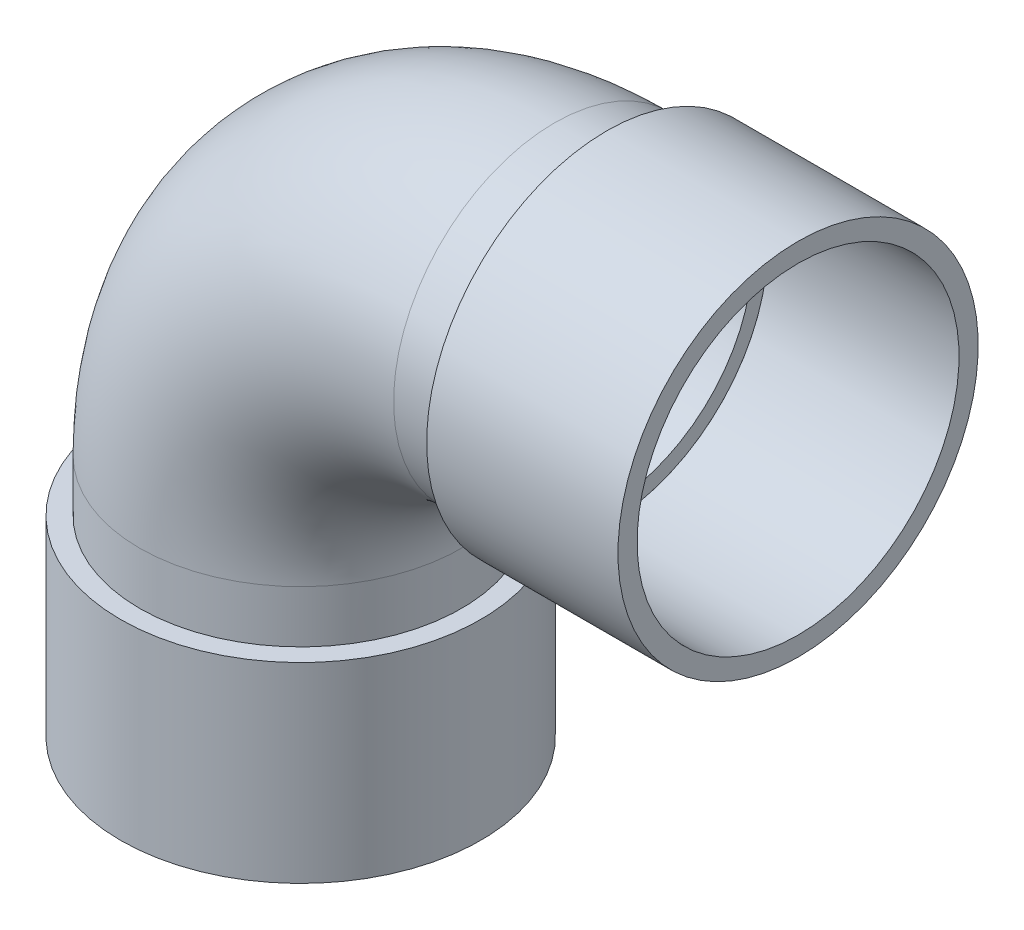
SolidWorks part; units mm, degrees
ref_plane "Alzado" through (0, 0, 0) normal (0, 0, 1) x (1, 0, 0)
ref_plane "Planta" through (0, 0, 0) normal (0, 1, 0) x (1, 0, 0)
ref_plane "Vista lateral" through (0, 0, 0) normal (1, 0, 0) x (0, 0, -1)
sketch "Croquis2" plane through (0, 0, 0) normal (0, 0, 1) x (1, 0, 0)
  line L0 (0, 0) -> (0, 27.27)
  line L1 (132.73, 160) -> (160, 160)
  arc A0 (0, 27.27) -> (132.73, 160) centre (132.73, 27.27) cw
  point P1 (0, 254)
  point P6 (0, 160)
  point P7 (-3.1791, 254)
  point P9 (0, 160)
  dimension "D3" = 132.73
  dimension "D1" = 160
  dimension "D2" = 160
sketch "Croquis3" plane through (0, 0, 0) normal (0, 1, 0) x (1, 0, 0)
  circle A0 centre (0, 0) radius 84.15
  circle A1 centre (0, 0) radius 76.2
  dimension "D1" = 168.3
  dimension "D2" = 152.4
sweep "Barrer1" add profiles "Croquis3" path "Croquis2"
sketch "Croquis4" plane through (160, 0, 0) normal (1, 0, 0) x (0, 0, -1)
  circle A0 centre (0, 160) radius 94.15
  circle A1 centre (0, 160) radius 84.15
  circle A2 centre (0, 160) radius 84.15
  dimension "D2" = 10
  dimension "D1" = 0
extrude "Saliente-Extruir1" add sketch "Croquis4" along normal blind 100 separate body
sketch "Croquis5" plane through (0, 0, 0) normal (0, -1, 0) x (1, 0, 0)
  circle A0 centre (0, 0) radius 94.15
  circle A1 centre (0, 0) radius 84.15
  circle A2 centre (0, 0) radius 84.15
  dimension "D2" = 10
  dimension "D1" = 0
extrude "Saliente-Extruir2" add sketch "Croquis5" along normal blind 100 separate body
